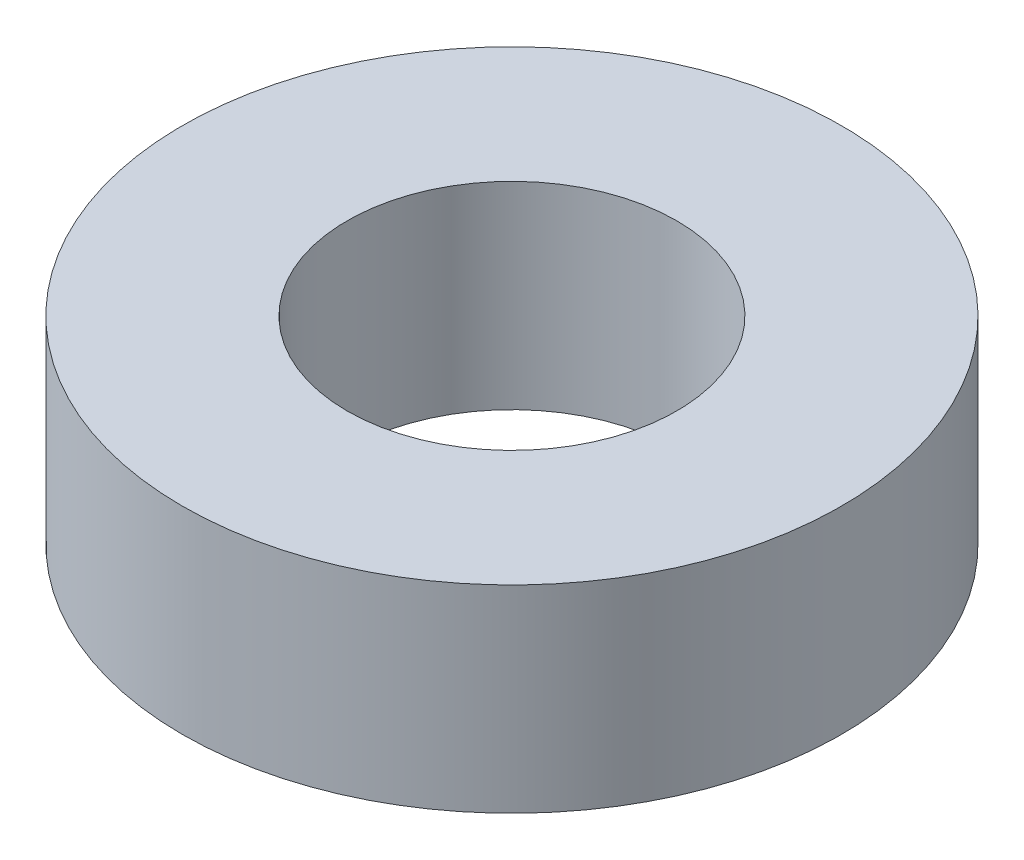
SolidWorks part; units mm, degrees
ref_plane "Front Plane" through (0, 0, 0) normal (0, 0, 1) x (1, 0, 0)
ref_plane "Top Plane" through (0, 0, 0) normal (0, 1, 0) x (1, 0, 0)
ref_plane "Right Plane" through (0, 0, 0) normal (1, 0, 0) x (0, 0, -1)
sketch "Sketch1" plane through (0, 0, 0) normal (0, 1, 0) x (1, 0, 0)
  circle A0 centre (0, 0) radius 5
  circle A1 centre (0, 0) radius 10
extrude "Boss-Extrude1" add sketch "Sketch1" along normal blind 6 contours A1 | A0
ref_axis "Axis1" through (0, 6, 0) along (0, -1, 0)
